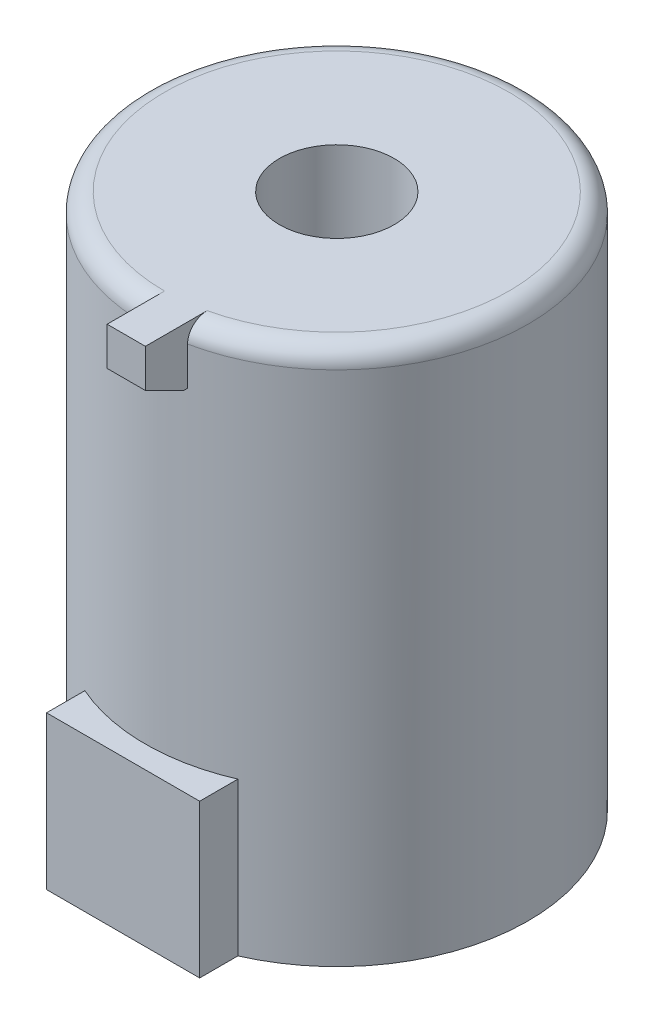
SolidWorks part; units mm, degrees
ref_plane "前基準面" through (0, 0, 0) normal (0, 0, 1) x (1, 0, 0)
ref_plane "上基準面" through (0, 0, 0) normal (0, 1, 0) x (1, 0, 0)
ref_plane "右基準面" through (0, 0, 0) normal (1, 0, 0) x (0, 0, -1)
sketch "草圖1" plane through (0, 0, 0) normal (0, 1, 0) x (1, 0, 0)
  circle A0 centre (0, 0) radius 50
  dimension "D1" = 100
extrude "填料-伸長1" add sketch "草圖1" along normal blind 140
sketch "草圖2" plane through (0, 0, 0) normal (0, -1, 0) x (1, 0, 0)
  line L0 (-20, -65.6591) -> (-20, 170.5003) construction
  line L1 (0, 0) -> (0, 63.8278) construction
  line L2 (-20, 45.8258) -> (20, 45.8258)
  line L3 (-20, 45.8258) -> (-20, 55.8258)
  line L4 (-20, 55.8258) -> (20, 55.8258)
  line L5 (20, 45.8258) -> (20, 55.8258)
  circle A0 centre (0, 0) radius 50 construction
  dimension "D1" = 20
  dimension "D2" = 40
  dimension "D3" = 10
extrude "填料-伸長2" add sketch "草圖2" against normal blind 40
sketch "草圖3" plane through (0, 140, 0) normal (0, 1, 0) x (1, 0, 0)
  circle A0 centre (0, 0) radius 15
  dimension "D1" = 30
extrude "除料-伸長1" cut sketch "草圖3" against normal blind 40
sketch "草圖4" plane through (0, 0, 0) normal (1, 0, 0) x (0, 0, -1)
  line L0 (-50, 140) -> (-60, 140)
  line L1 (50, 140) -> (-50, 140) construction
  line L2 (-60, 140) -> (-60, 130)
  line L3 (-60, 130) -> (-50, 125)
  line L4 (-50, 140) -> (-50, 40) construction
  line L5 (-50, 140) -> (-44.5876, 140)
  line L6 (-44.5876, 140) -> (-44.5876, 125)
  line L7 (-44.5876, 125) -> (-50, 125)
  dimension "D1" = 10
  dimension "D2" = 10
  dimension "D3" = 15
extrude "填料-伸長4" add sketch "草圖4" along normal blind 10
fillet "圓角2" radius 5 1 edges at (-5.0254, 140, -49.7468)
